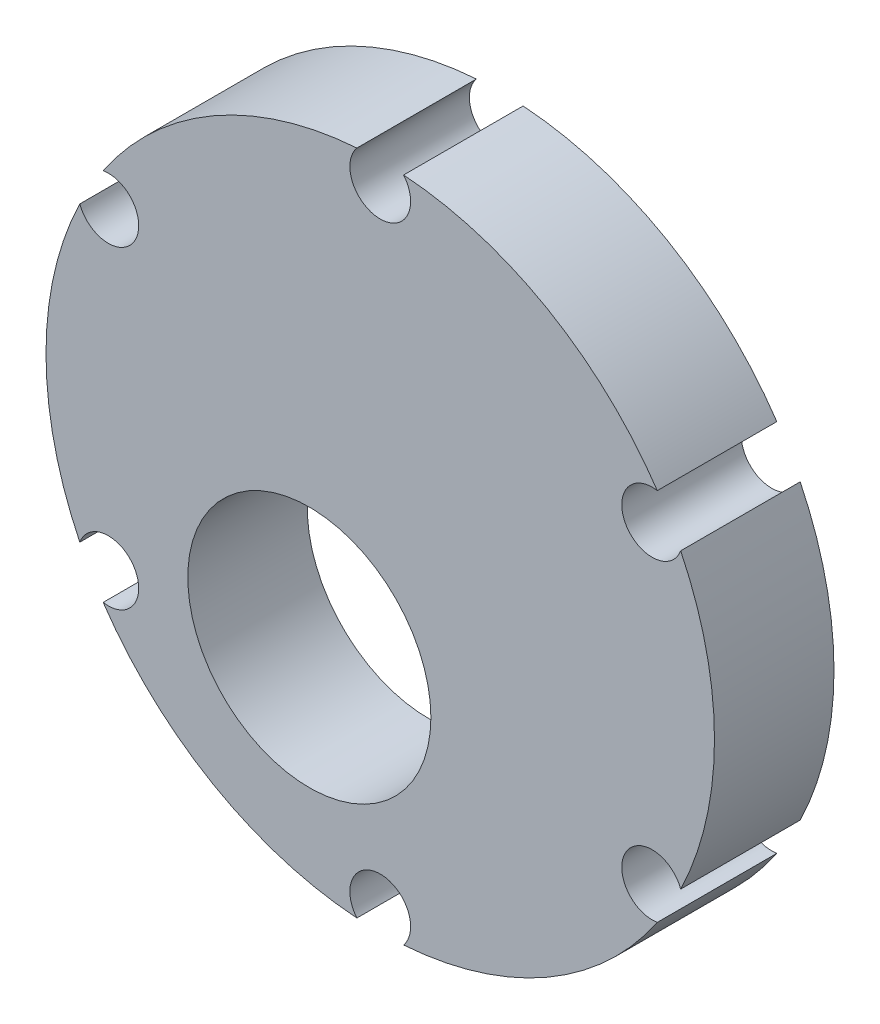
SolidWorks part; units mm, degrees
ref_plane "Front Plane" through (0, 0, 0) normal (0, 0, 1) x (1, 0, 0)
ref_plane "Top Plane" through (0, 0, 0) normal (0, 1, 0) x (1, 0, 0)
ref_plane "Right Plane" through (0, 0, 0) normal (1, 0, 0) x (0, 0, -1)
sketch "Sketch1" plane through (0, 0, 0) normal (0, 0, 1) x (1, 0, 0)
  circle A0 centre (0, 0) radius 16.5
  dimension "D1" = 33
extrude "Boss-Extrude1" add sketch "Sketch1" along normal blind 5.9
sketch "Sketch2" plane through (0, 0, 5.9) normal (0, 0, 1) x (1, 0, 0)
  circle A0 centre (0, 15.5) radius 1.5
  circle A1 centre (13.4234, 7.75) radius 1.5
  circle A2 centre (13.4234, -7.75) radius 1.5
  circle A3 centre (0, -15.5) radius 1.5
  circle A4 centre (-13.4234, -7.75) radius 1.5
  circle A5 centre (-13.4234, 7.75) radius 1.5
  point P15 (0, 0)
  dimension "D1" = 3
  dimension "D2" = 15.5
  dimension "D3" = 6
extrude "Cut-Extrude1" cut sketch "Sketch2" against normal through all
sketch "Sketch3" plane through (0, 0, 5.9) normal (0, 0, 1) x (1, 0, 0)
  line L0 (-3.5, -6.0622) -> (0, 0) construction
  line L1 (0, 0) -> (0, -15.5) construction
  circle A0 centre (-3.5, -6.0622) radius 6
  dimension "D1" = 12
  dimension "D2" = 30
  dimension "D3" = 7
extrude "Cut-Extrude2" cut sketch "Sketch3" against normal through all
equation "\"smallPulleyTeeth\"= 15"
equation "\"largePulleyTeeth\"= 40"
equation "\"eighthThick\"= 2.9mm"
equation "\"sixteenthThick\" = 1.7mm"
equation "\"wheelEighthThick\"=3.0mm"
equation "\"quarterThick\"=5.9mm"
equation "\"OD\" = 145mm"
equation "\"puckAngle\" = 60.5deg"
equation "\"puckDiam\" = 76.5mm"
equation "\"axlePress\" = 5.9mm"
equation "\"D1@Boss-Extrude1\"=\"quarterThick\""
